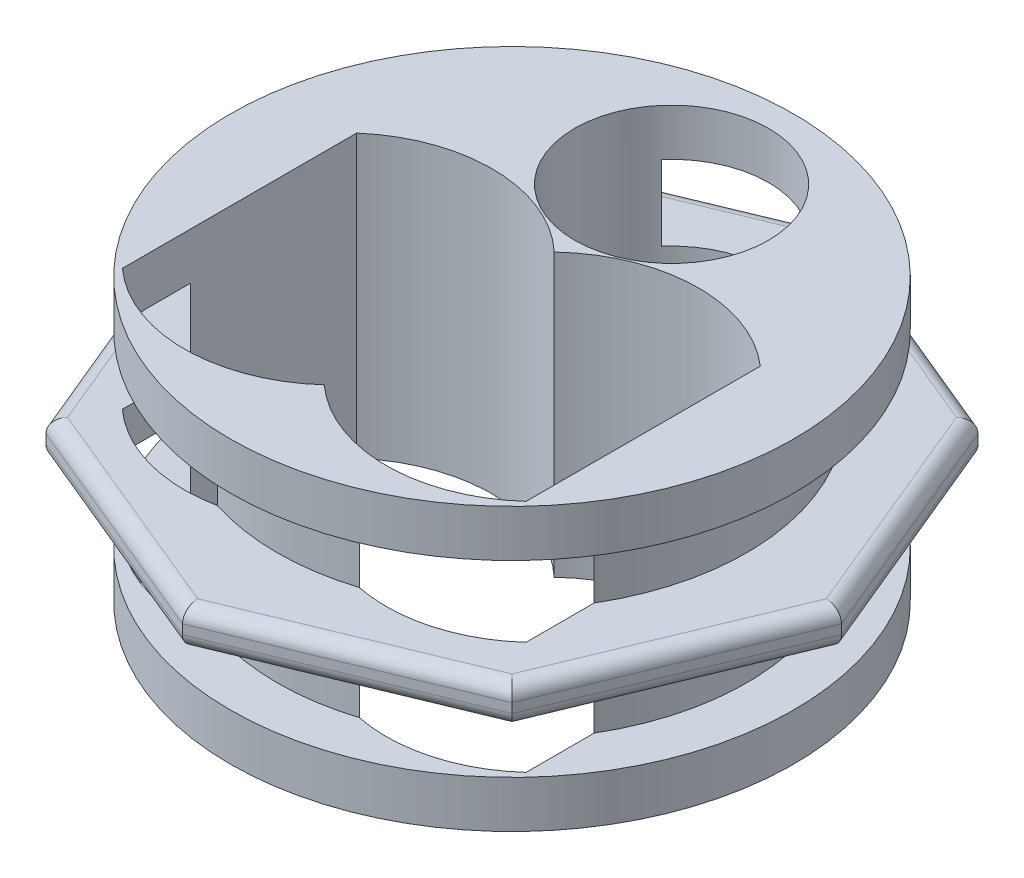
SolidWorks part; units mm, degrees
ref_plane "Front Plane" through (0, 0, 0) normal (0, 0, 1) x (1, 0, 0)
ref_plane "Top Plane" through (0, 0, 0) normal (0, 1, 0) x (1, 0, 0)
ref_plane "Right Plane" through (0, 0, 0) normal (1, 0, 0) x (0, 0, -1)
sketch "Sketch3" plane through (0, 0, 0) normal (0, 1, 0) x (1, 0, 0)
  line L1 (35.1, 0) -> (24.8194, 24.8194)
  line L2 (24.8194, 24.8194) -> (0, 35.1)
  line L3 (0, 35.1) -> (-24.8194, 24.8194)
  line L4 (-24.8194, 24.8194) -> (-35.1, 0)
  line L5 (-35.1, 0) -> (-24.8194, -24.8194)
  line L6 (-24.8194, -24.8194) -> (0, -35.1)
  line L7 (0, -35.1) -> (24.8194, -24.8194)
  line L8 (24.8194, -24.8194) -> (35.1, 0)
  circle A0 centre (0, 0) radius 32.4282 construction
  dimension "D1" = 35.1
extrude "Boss-Extrude1" add sketch "Sketch3" along normal blind 2
ref_axis "Axis2" through (0, 2, -35.1) along (0, 0, 1)
ref_axis "Axis3" through (0, 0, -35.1) along (0, 0, 1)
ref_plane "Plane1" through (0, 0, 0) normal (-1, 0, 0) x (0, 0, 1)
sketch "Sketch9" plane through (0, 2, 0) normal (0, 1, 0) x (1, 0, 0)
  line L0 (0, 38.0801) -> (0, -38.8207)
  line L1 (0, 27.2715) -> (0, -27.2715) construction
sketch "Sketch10" plane through (0, 2, 0) normal (0, 1, 0) x (1, 0, 0)
  line L1 (0, 38.0801) -> (47.253, 38.0801)
  line L2 (0, 38.0801) -> (0, -41.0679)
  line L3 (0, -41.0679) -> (47.253, -41.0679)
  line L4 (47.253, 38.0801) -> (47.253, -41.0679)
sketch "Sketch12" plane through (0, 2, 0) normal (0, 1, 0) x (1, 0, 0)
  circle A0 centre (0, 0) radius 25
extrude "Boss-Extrude2" add sketch "Sketch12" along normal blind 8 contours A0
sketch "Sketch17" plane through (0, 10, 0) normal (0, 1, 0) x (1, 0, 0)
  line L0 (0, 38.0801) -> (0, -38.8207) construction
  circle A0 centre (0, 17) radius 10.33
extrude "Cut-Extrude6" cut sketch "Sketch17" against normal blind 36 and the other way blind 9.8561 contours A0
sketch "Sketch23" plane through (0, 10, 0) normal (0, 1, 0) x (1, 0, 0)
  line L2 (-22.0422, 4.5) -> (-22.0422, -20)
  line L4 (-0.0422, 4.5) -> (-0.0422, -20)
  arc A0 (-22.0422, 4.5) -> (-0.0422, 4.5) centre (-11.0422, -7.119) cw
  arc A1 (-22.0422, -20) -> (-0.0422, -20) centre (-11.0422, -8.381) ccw
  point P6 (14.8691, -17.9405)
  dimension "D1" = 22
  dimension "D2" = 24.5
sketch "Sketch24" plane through (0, 10, 0) normal (0, 1, 0) x (1, 0, 0)
  line L2 (0, -30.0031) -> (33.426, -30.0031)
  line L3 (0, -30.0031) -> (0, 37.3911)
  line L4 (0, 37.3911) -> (33.426, 37.3911)
  line L5 (33.426, -30.0031) -> (33.426, 37.3911)
  point P0 (0, 0)
sketch "Sketch25" plane through (0, 10, 0) normal (0, 1, 0) x (1, 0, 0)
  circle A0 centre (0, 0) radius 30
extrude "Boss-Extrude3" add sketch "Sketch25" along normal blind 5
sketch "Sketch26" plane through (0, 15, 0) normal (0, 1, 0) x (1, 0, 0)
  line L0 (0, 38.0801) -> (0, -38.8207) construction
  circle A0 centre (0, 17) radius 10.33
extrude "Cut-Extrude9" cut sketch "Sketch26" against normal blind 5 contours A0
sketch "Sketch27" plane through (0, 15, 0) normal (0, 1, 0) x (1, 0, 0)
  line L0 (0, 38.0801) -> (0, -38.8207) construction
  line L2 (0, -20) -> (0, 4.5)
  line L4 (-21.5, -20) -> (-21.5, 4.9537)
  arc A0 (-21.5, 4.9537) -> (0, 4.5) centre (-11, -7.119) cw
  arc A1 (-21.5, -20) -> (0, -20) centre (-10.75, -8.1494) ccw
extrude "Cut-Extrude10" cut sketch "Sketch27" against normal blind 45
mirror "Mirror8" about plane through (0, 0, 0) normal (-1, 0, 0) of "Cut-Extrude10"
fillet "Fillet3" radius 1.5 8 edges at (12.4097, 2, 29.9597) (29.9597, 2, 12.4097) (-12.4097, 2, 29.9597) (-29.9597, 2, 12.4097) (-29.9597, 2, -12.4097) (29.9597, 2, -12.4097) (-12.4097, 2, -29.9597) (12.4097, 2, -29.9597)
mirror "Mirror9" about plane through (0, 0, 0) normal (0, 1, 0) of "Cut-Extrude10", "Cut-Extrude6", "Mirror8", "Fillet3", "Boss-Extrude2", "Boss-Extrude3", "Boss-Extrude1"
sketch "Sketch29" plane through (0, -15, 0) normal (0, -1, 0) x (1, 0, 0)
  circle A0 centre (0, -17) radius 10.33
extrude "Cut-Extrude11" cut sketch "Sketch29" against normal blind 5 contours A0
